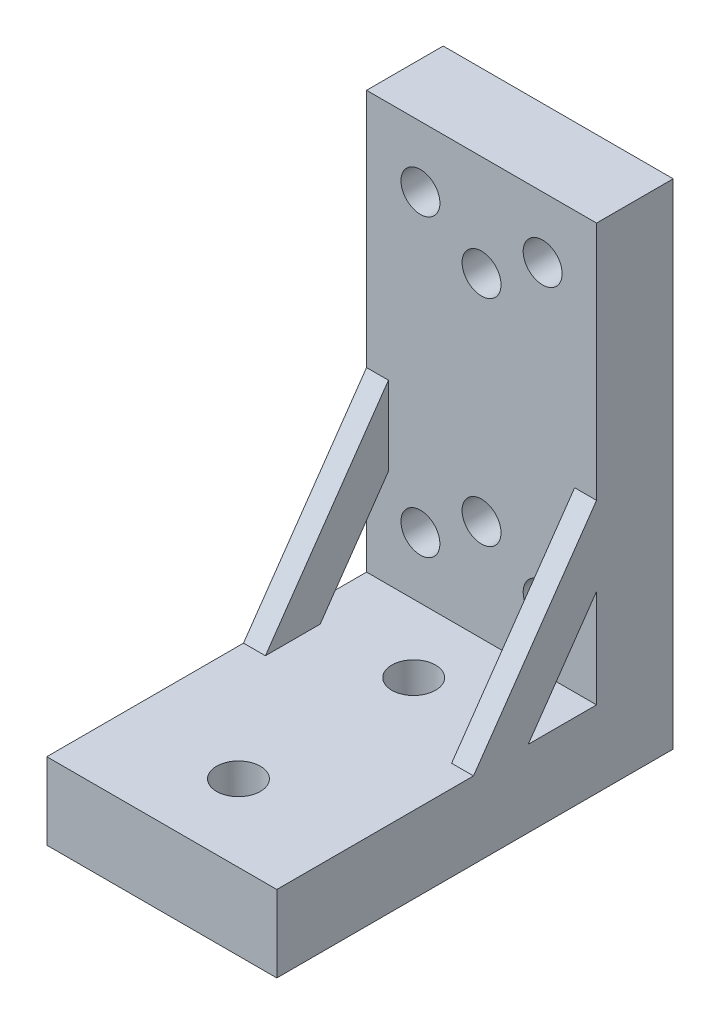
SolidWorks part; units mm, degrees
material "AISI 1020"
ref_plane "Front Plane" through (0, 0, 0) normal (0, 0, 1) x (1, 0, 0)
ref_plane "Top Plane" through (0, 0, 0) normal (0, 1, 0) x (1, 0, 0)
ref_plane "Right Plane" through (0, 0, 0) normal (1, 0, 0) x (0, 0, -1)
sketch "Sketch1" plane through (0, 0, 0) normal (0, 0, 1) x (1, 0, 0)
  line L0 (-10.5, 0) -> (10.5, 0) construction
  line L1 (-10.5, 19.05) -> (10.5, 19.05)
  line L2 (-10.5, 19.05) -> (-10.5, -19.05)
  line L3 (-10.5, -19.05) -> (10.5, -19.05)
  line L4 (10.5, 19.05) -> (10.5, -19.05)
  line L5 (-5.58, 13.47) -> (5.58, 13.47) construction
  circle A0 centre (-5.58, 13.47) radius 1.778
  circle A1 centre (5.58, 13.47) radius 1.778
  circle A2 centre (0, 9.805) radius 1.778
  circle A3 centre (5.58, -13.47) radius 1.778
  circle A4 centre (0, -9.805) radius 1.778
  circle A5 centre (-5.58, -13.47) radius 1.778
  point P4 (0, 19.05)
  point P6 (-10.5, 0)
  point P15 (0, 13.47)
  dimension "D3" = 3.556
  dimension "D1" = 38.1
  dimension "D2" = 21
  dimension "D4" = 26.94
  dimension "D5" = 26.94
  dimension "D6" = 19.61
  dimension "D7" = 11.16
extrude "Boss-Extrude1" add sketch "Sketch1" along normal blind 7
sketch "Sketch3" plane through (0, 0, 0) normal (0, 0, -1) x (-1, 0, 0)
  line L0 (10.5, -19.05) -> (-10.5, -19.05)
  line L1 (10.5, -19.05) -> (10.5, -26.05)
  line L2 (-10.5, -19.05) -> (-10.5, -26.05)
  line L3 (10.5, -26.05) -> (-10.5, -26.05)
  dimension "D1" = 7
extrude "Boss-Extrude2" add sketch "Sketch3" against normal blind 36.195
sketch "Sketch4" plane through (0, -26.05, 0) normal (0, -1, 0) x (1, 0, 0)
  line L0 (0, 0) -> (0, 36.195) construction
  line L1 (10.5, 0) -> (-10.5, 0) construction
  line L2 (10.5, 36.195) -> (-10.5, 36.195) construction
  line L3 (-10.5, 36.195) -> (10.5, 36.195) construction
  circle A0 centre (0, 13.195) radius 2
  circle A1 centre (0, 29.195) radius 2
  dimension "D3" = 4
  dimension "D1" = 7
  dimension "D2" = 16
extrude "Cut-Extrude1" cut sketch "Sketch4" against normal blind 10.5
sketch "Sketch5" plane through (10.5, 0, 0) normal (1, 0, 0) x (0, 0, -1)
  line L0 (-18.0975, -26.05) -> (0, 0)
  line L1 (-36.195, -26.05) -> (0, -26.05) construction
  line L2 (-23.0975, -26.05) -> (0, 7.1971)
  line L3 (0, -26.05) -> (0, 19.05) construction
  line L4 (0, 7.1971) -> (0, 0)
  line L5 (-18.0975, -26.05) -> (-23.0975, -26.05)
  dimension "D1" = 360
  dimension "D2" = 5
extrude "Boss-Extrude3" add sketch "Sketch5" against normal blind 2
extrude "Boss-Extrude4" add sketch "Sketch5<2>" against normal blind 2 from offset 19 offset against normal yes
sketch "Sketch5<2>" plane through (10.5, 0, 0) normal (1, 0, 0) x (0, 0, -1) same geometry as "Sketch5"
